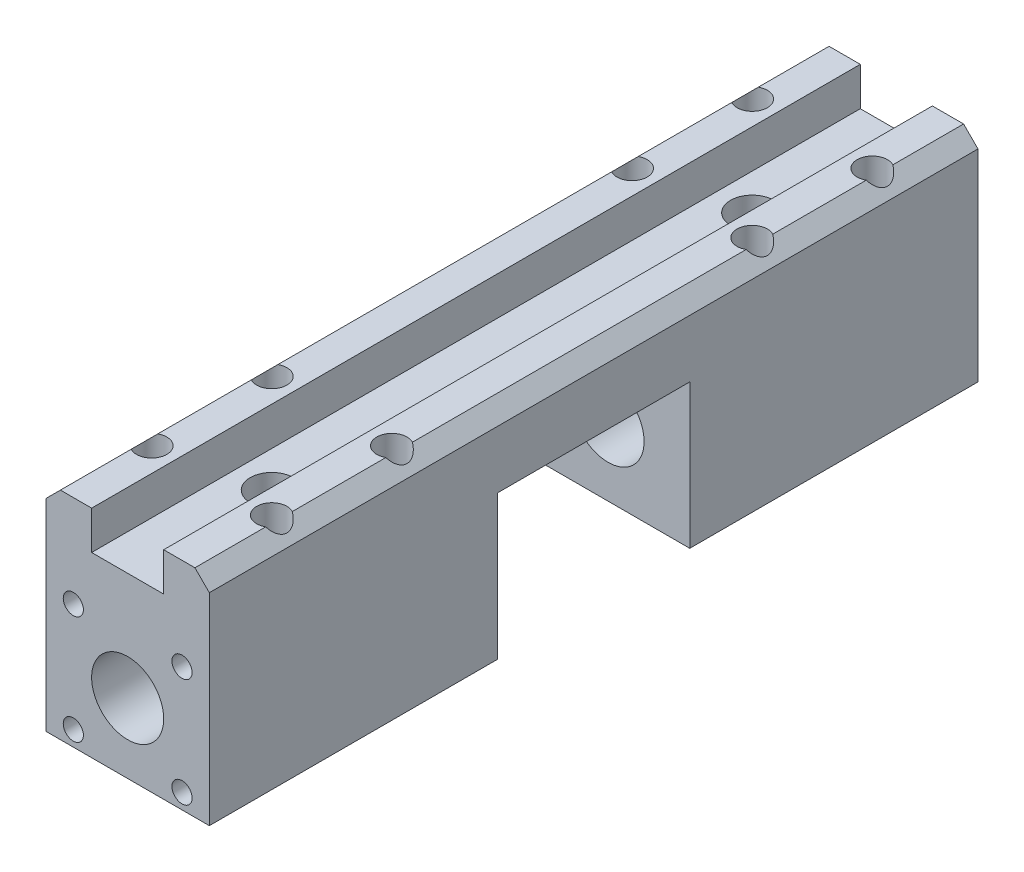
SolidWorks part; units mm, degrees
material "3.1355 (EN-AW 2024)"
ref_plane "Спереди" through (0, 0, 0) normal (0, 0, 1) x (1, 0, 0)
ref_plane "Сверху" through (0, 0, 0) normal (0, 1, 0) x (1, 0, 0)
ref_plane "Справа" through (0, 0, 0) normal (1, 0, 0) x (0, 0, -1)
sketch "Эскиз1" plane through (0, 0, 0) normal (0, 1, 0) x (1, 0, 0)
  line L1 (-17, 80) -> (17, 80)
  line L2 (-17, 80) -> (-17, -80)
  line L3 (-17, -80) -> (17, -80)
  line L4 (17, 80) -> (17, -80)
  line L5 (-17, 80) -> (17, -80) construction
  line L6 (-17, -80) -> (17, 80) construction
  point P0 (0, 0)
  dimension "D1" = 160
  dimension "D2" = 34
extrude "База" add sketch "Эскиз1" along normal blind 45
hole_wizard "Каретки M3" positions "Эскиз2" profile "Эскиз3" countersink size "M3" standard "DIN" end condition through all
sketch "Эскиз2" plane through (0, 45, 0) normal (0, 1, 0) x (1, 0, 0)
  line L0 (-12.5, -37.5) -> (0, -37.5) construction
  line L1 (0, -37.5) -> (12.5, -37.5) construction
  line L2 (12.5, -37.5) -> (12.5, -62.5) construction
  line L5 (-50, 0) -> (50, 0) construction
  line L6 (12.5, 37.5) -> (12.5, 62.5) construction
  line L7 (0, 37.5) -> (12.5, 37.5) construction
  line L8 (-12.5, 37.5) -> (0, 37.5) construction
  point P0 (-12.5, -62.5)
  point P2 (12.5, -62.5)
  point P4 (12.5, -37.5)
  point P6 (-12.5, -37.5)
  point P23 (-12.5, 62.5)
  point P27 (-12.5, 37.5)
  point P30 (12.5, 37.5)
  point P33 (12.5, 62.5)
  point P34 (-12.5, 62.5)
  point P35 (12.5, -50)
  dimension "D1" = 25
  dimension "D2" = 25
  dimension "D3" = 50
sketch "Эскиз3" plane through (-12.5, 45, 62.5) normal (1, 0, 0) x (0, 0, 1)
  line L0 (0, 0) -> (0, 45)
  line L1 (0, 45) -> (1.7, 45)
  line L2 (1.7, 45) -> (1.7, 28.45)
  line L3 (1.7, 28.45) -> (3.15, 27)
  line L4 (3.15, 27) -> (3.15, 0)
  line L6 (3.15, 0) -> (0, 0)
  line L7 (-1.7, 28.45) -> (-3.15, 27) construction
  line L11 (0, -6.35) -> (0, 107.95) construction
  dimension "Диаметр сквозного отверстия" = 3.4
  dimension "Глубина сквозного отверстия" = 45
  dimension "Диаметр зенковки" = 6.3
  dimension "Угол зенковки" = 90
  dimension "Утопленность" = 27
sketch "Эскиз7" plane through (0, 45, 0) normal (0, 1, 0) x (1, 0, 0)
  line L0 (17, 80) -> (-17, 80) construction
  line L1 (-7.5, -80) -> (7.5, -80)
  line L2 (-7.5, -80) -> (-7.5, 80)
  line L3 (-7.5, 80) -> (7.5, 80)
  line L4 (7.5, -80) -> (7.5, 80)
  line L5 (-7.5, -80) -> (7.5, 80) construction
  line L6 (-7.5, 80) -> (7.5, -80) construction
  point P0 (0, 0)
  dimension "D1" = 15
extrude "Посадка вертикальной плиты" cut sketch "Эскиз7" against normal blind 8
chamfer "Фаска1" distance 3 angle 45 2 edges at (-17, 45, 0) (17, 45, 0)
sketch "Эскиз8" plane through (0, 0, 80) normal (0, 0, 1) x (1, 0, 0)
  circle A0 centre (0, 14.5) radius 7.5
  dimension "D1" = 15
  dimension "D2" = 14.5
extrude "Вырез-Вытянуть1" cut sketch "Эскиз8" against normal through all
hole_wizard "Верхняя плита M6" positions "Эскиз5" profile "Эскиз6" counterbore size "M8" standard "DIN" end condition through all
sketch "Эскиз5" plane through (0, 0, 0) normal (0, -1, 0) x (-1, 0, 0)
  line L14 (0, -50) -> (0, 0) construction
  line L15 (0, 0) -> (0, 50) construction
  line L18 (12.5, 62.5) -> (12.5, 37.5) construction
  line L21 (12.5, -62.5) -> (12.5, -37.5) construction
  point P0 (0, -50)
  point P2 (0, 50)
  point P54 (12.5, 50)
  point P55 (12.5, -50)
sketch "Эскиз6" plane through (0, 0, 50) normal (1, 0, 0) x (0, 0, -1)
  line L0 (0, 0) -> (0, 45)
  line L1 (0, 45) -> (4.5, 45)
  line L3 (4.5, 45) -> (4.5, 28.6)
  line L4 (4.5, 28.6) -> (7.5, 28.6)
  line L5 (7.5, 28.6) -> (7.5, 0)
  line L7 (7.5, 0) -> (0, 0)
  line L11 (0, -6.35) -> (0, 107.95) construction
  dimension "Диаметр сквозного отверстия" = 9
  dimension "Глубина сквозного отверстия" = 45
  dimension "Диаметр цековки" = 15
  dimension "Глубина цековки" = 28.6
sketch "Эскиз10" plane through (17, 0, 0) normal (1, 0, 0) x (0, 0, -1)
  line L0 (-80, 0) -> (80, 0) construction
  line L1 (-20, 0) -> (20, 0)
  line L2 (-20, 0) -> (-20, 30)
  line L3 (-20, 30) -> (20, 30)
  line L4 (20, 0) -> (20, 30)
  point P6 (0, 0)
  dimension "D1" = 30
  dimension "D2" = 40
extrude "Вырез-Вытянуть3" cut sketch "Эскиз10" against normal through all
hole_wizard "Гайка-1204" positions "Эскиз11" profile "Эскиз12" tap size "M5" standard "DIN" end condition through all
sketch "Эскиз11" plane through (0, 0, 20) normal (0, 0, -1) x (-1, 0, 0)
  line L0 (11.3137, 25.8137) -> (0, 25.8137) construction
  line L1 (0, 25.8137) -> (-11.3137, 25.8137) construction
  line L2 (-11.3137, 25.8137) -> (-11.3137, 14.5) construction
  line L3 (-11.3137, 14.5) -> (-11.3137, 3.1863) construction
  point P0 (11.3137, 25.8137)
  point P3 (11.3137, 3.1863)
  point P6 (-11.3137, 3.1863)
  point P12 (-11.3137, 25.8137)
  dimension "D1" = 22.6274
  dimension "D2" = 14.5
cosmetic thread "Отверстие резьбы1" parameters "D2"=5
cosmetic thread "Отверстие резьбы2" parameters "D2"=5
cosmetic thread "Отверстие резьбы3" parameters "D2"=5
cosmetic thread "Отверстие резьбы4" parameters "D2"=5
sketch "Эскиз12" plane through (-11.3137, 25.8137, 20) normal (1, 0, 0) x (0, 1, 0)
  line L0 (0, 0) -> (0, 60)
  line L1 (0, 60) -> (2.1, 60)
  line L2 (2.1, 60) -> (2.1, 0.425)
  line L3 (2.1, 0.425) -> (2.525, 0)
  line L5 (2.525, 0) -> (0, 0)
  line L6 (-2.1, 0.425) -> (-2.525, 0) construction
  line L11 (0, -6.35) -> (0, 107.95) construction
  dimension "Диаметр проходного сверла" = 4.2
  dimension "Глубина проходного сверла" = 60
  dimension "Диаметр передней зенковки" = 5.05
  dimension "Угол передней зенковки" = 90
